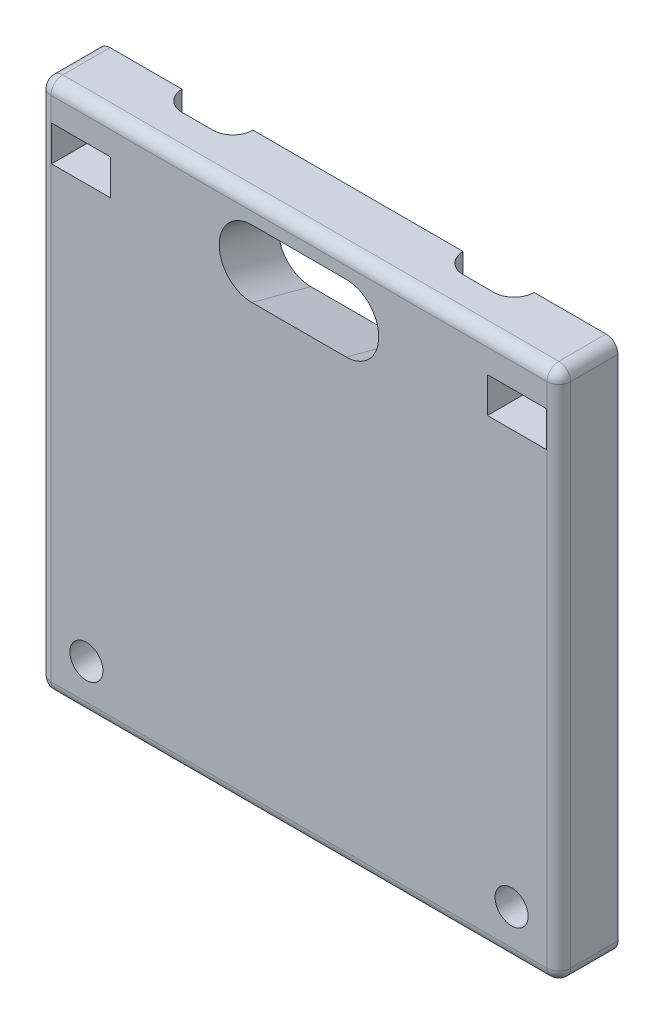
SolidWorks part; units mm, degrees
ref_plane "Front Plane" through (0, 0, 0) normal (0, 0, 1) x (1, 0, 0)
ref_plane "Top Plane" through (0, 0, 0) normal (0, 1, 0) x (1, 0, 0)
ref_plane "Right Plane" through (0, 0, 0) normal (1, 0, 0) x (0, 0, -1)
sketch "Sketch1" plane through (0, 0, 0) normal (0, 0, 1) x (1, 0, 0)
  line L1 (-22, 22.5) -> (22, 22.5)
  line L2 (-22, 22.5) -> (-22, -22.5)
  line L3 (-22, -22.5) -> (22, -22.5)
  line L4 (22, 22.5) -> (22, -22.5)
  line L5 (-22, 22.5) -> (22, -22.5) construction
  line L6 (-22, -22.5) -> (22, 22.5) construction
  point P0 (0, 0)
  dimension "D1" = 44
  dimension "D2" = 45
extrude "Base" add sketch "Sketch1" along normal blind 5
sketch "Sketch2" plane through (0, 22.5, 0) normal (0, 1, 0) x (1, 0, 0)
  line L0 (22, 0) -> (-22, 0) construction
  line L1 (-14.9, 0) -> (-8.9, 0)
  line L2 (0, 0) -> (0, -5) construction
  line L3 (22, -5) -> (-22, -5) construction
  line L5 (-14.9, 0) -> (-14.9, -5) construction
  line L6 (-13.2, -1.7) -> (-10.6, -1.7)
  line L7 (13.2, -1.7) -> (10.6, -1.7)
  line L8 (14.9, 0) -> (8.9, 0)
  arc A2 (-14.9, 0) -> (-13.2, -1.7) centre (-13.2, 0) ccw
  arc A3 (-10.6, -1.7) -> (-8.9, 0) centre (-10.6, 0) ccw
  arc A4 (14.9, 0) -> (13.2, -1.7) centre (13.2, 0) cw
  arc A5 (10.6, -1.7) -> (8.9, 0) centre (10.6, 0) cw
  point P0 (-11.9, 0)
  dimension "D1" = 6
  dimension "D2" = 11.9
  dimension "D3" = 1.7
extrude "Wire Grooves" cut sketch "Sketch2" against normal through all
sketch "Sketch4" plane through (0, 0, 0) normal (0, 0, -1) x (-1, 0, 0)
  line L0 (0, 22.5) -> (0, -22.5) construction
  line L3 (-22, 16.5291) -> (22, 16.5291) construction
  line L4 (-22, -22.5) -> (-22, 22.5) construction
  line L5 (22, 22.5) -> (22, -22.5) construction
  line L6 (-8.9, 22.5) -> (8.9, 22.5) construction
  line L8 (8.9, -22.5) -> (-8.9, -22.5) construction
  dimension "D1" = 5.9709
ref_plane "Screw Insertion Hole Reference" through (0, 1.1072, 4.1323) normal (0, -0.2588, -0.9659) x (-1, 0, 0)
sketch "Sketch3" plane through (0, 0.5961, 4.2692) normal (0, -0.2588, -0.9659) x (-1, 0, 0)
  line L0 (0, 0.5291) -> (0, 22.2625) construction
  line L1 (-4, 16.2925) -> (4, 16.2925) construction
  line L2 (-8.9, 22.2625) -> (8.9, 22.2625) construction
  line L3 (-4, 19.0425) -> (4, 19.0425)
  line L4 (-4, 13.5425) -> (4, 13.5425)
  arc A1 (-4, 19.0425) -> (-4, 13.5425) centre (-4, 16.2925) ccw
  arc A2 (4, 13.5425) -> (4, 19.0425) centre (4, 16.2925) ccw
  point P5 (0, 16.2925)
  dimension "D1" = 5.97
  dimension "D2" = 2.75
  dimension "D3" = 8
extrude "Screw Insertion Hole" cut sketch "Sketch3" against normal through all both and the other way through all
sketch "Sketch5" plane through (0, 0, 0) normal (0, 0, -1) x (-1, 0, 0)
  line L0 (-18.45, 22.5) -> (-18.45, -22.5) construction
  line L1 (-22, 22.5) -> (-14.9, 22.5) construction
  line L2 (-14.9, -22.5) -> (-22, -22.5) construction
  line L3 (0, 22.5) -> (0, -22.5) construction
  line L7 (-20.95, 19.5) -> (-15.95, 19.5)
  line L8 (-20.95, 19.5) -> (-20.95, 16.5)
  line L9 (-20.95, 16.5) -> (-15.95, 16.5)
  line L10 (-15.95, 19.5) -> (-15.95, 16.5)
  line L11 (-20.95, 19.5) -> (-15.95, 16.5) construction
  line L12 (-20.95, 16.5) -> (-15.95, 19.5) construction
  line L16 (-8.9, 22.5) -> (8.9, 22.5) construction
  line L17 (8.9, -22.5) -> (-8.9, -22.5) construction
  line L18 (20.95, 16.5) -> (15.95, 16.5)
  line L19 (15.95, 19.5) -> (15.95, 16.5)
  line L20 (20.95, 19.5) -> (15.95, 19.5)
  line L21 (20.95, 19.5) -> (20.95, 16.5)
  point P12 (-18.45, 18)
  dimension "D1" = 5
  dimension "D2" = 3
  dimension "D3" = 3
extrude "Zip Tie Slots" cut sketch "Sketch5" against normal through all
sketch "Sketch6" plane through (0, 0, 0) normal (0, 0, -1) x (-1, 0, 0)
  line L1 (-22, -22.5) -> (-22, 22.5) construction
  line L2 (-14.9, -22.5) -> (-22, -22.5) construction
  line L4 (0, 22.5) -> (0, -22.5) construction
  line L6 (-8.9, 22.5) -> (8.9, 22.5) construction
  line L7 (8.9, -22.5) -> (-8.9, -22.5) construction
  circle A0 centre (-18, -18.5) radius 1.4
  circle A2 centre (18, -18.5) radius 1.4
  dimension "D1" = 2.8
  dimension "D2" = 4
  dimension "D3" = 4
extrude "Mount Clamping Holes" cut sketch "Sketch6" against normal through all
fillet "Edge Fillets" radius 1 8 edges at (-22, 0, 5) (22, 0, 5) (0, -22.5, 5) (0, 22.5, 5) (22, 22.5, 2.5) (22, -22.5, 2.5) (-22, -22.5, 2.5) (-22, 22.5, 2.5)
